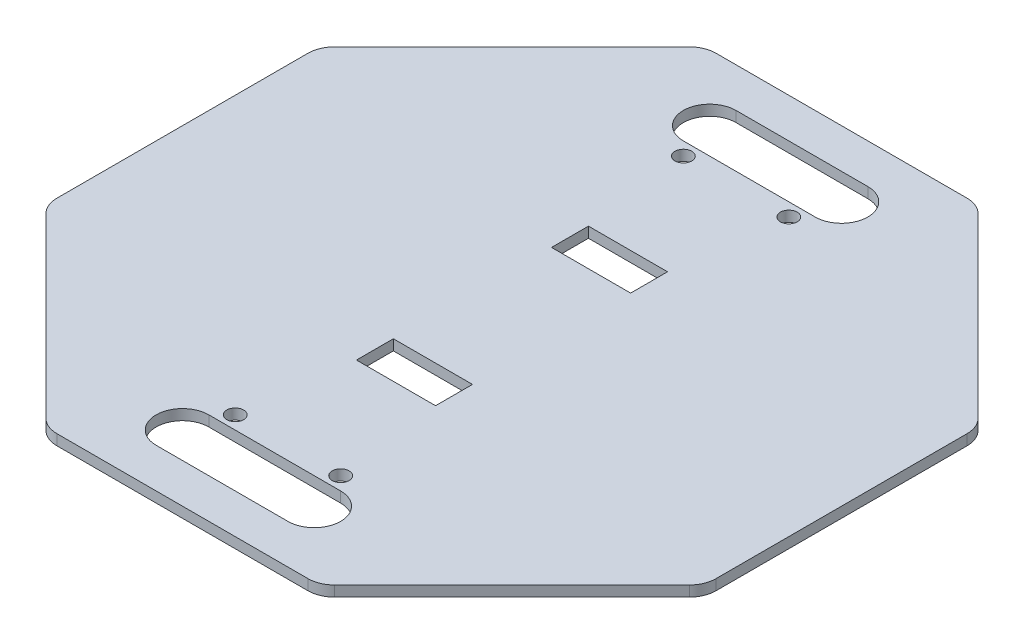
SolidWorks part; units mm, degrees
ref_plane "Front Plane" through (0, 0, 0) normal (0, 0, 1) x (1, 0, 0)
ref_plane "Top Plane" through (0, 0, 0) normal (0, 1, 0) x (1, 0, 0)
ref_plane "Right Plane" through (0, 0, 0) normal (1, 0, 0) x (0, 0, -1)
sketch "Sketch1" plane through (0, 0, 0) normal (0, 1, 0) x (1, 0, 0)
  line L0 (0, 67.6495) -> (0, -67.6495) construction
  line L1 (-67.6495, 0) -> (67.6495, 0) construction
  line L2 (62.5, 25.8883) -> (62.5, -25.8883)
  line L3 (-25.8883, 62.5) -> (25.8883, 62.5)
  line L4 (0, 0) -> (62.5, 25.8883) construction
  line L5 (-25.8883, 62.5) -> (0, 0) construction
  line L6 (-25.8883, -62.5) -> (25.8883, -62.5)
  line L7 (-62.5, 25.8883) -> (-62.5, -25.8883)
  line L8 (12.5, -50) -> (-12.5, -50) construction
  line L9 (12.5, -55) -> (-12.5, -55)
  line L10 (12.5, -45) -> (-12.5, -45)
  line L11 (12.5, 50) -> (-12.5, 50) construction
  line L12 (12.5, 55) -> (-12.5, 55)
  line L13 (12.5, 45) -> (-12.5, 45)
  line L14 (14.3249, -42.5) -> (-21.367, -42.5) construction
  line L15 (-7.5, -22) -> (7.5, -22)
  line L16 (-7.5, -22) -> (-7.5, -15)
  line L17 (-7.5, -15) -> (7.5, -15)
  line L18 (7.5, -22) -> (7.5, -15)
  line L19 (-7.5, -22) -> (7.5, -15) construction
  line L20 (-7.5, -15) -> (7.5, -22) construction
  line L21 (-7.5, 22) -> (-7.5, 15)
  line L22 (-7.5, 22) -> (7.5, 22)
  line L23 (7.5, 22) -> (7.5, 15)
  line L24 (-7.5, 15) -> (7.5, 15)
  line L25 (25.8883, -62.5) -> (62.5, -25.8883)
  line L26 (62.5, 25.8883) -> (25.8883, 62.5)
  line L27 (-25.8883, 62.5) -> (-62.5, 25.8883)
  line L28 (-62.5, -25.8883) -> (-25.8883, -62.5)
  circle A0 centre (0, 0) radius 67.6495
  arc A1 (12.5, -55) -> (12.5, -45) centre (12.5, -50) ccw
  arc A2 (-12.5, -45) -> (-12.5, -55) centre (-12.5, -50) ccw
  arc A3 (12.5, 55) -> (12.5, 45) centre (12.5, 50) cw
  arc A4 (-12.5, 45) -> (-12.5, 55) centre (-12.5, 50) cw
  circle A5 centre (10, -42.5) radius 1.6
  circle A6 centre (-10, -42.5) radius 1.6
  circle A7 centre (-10, 42.5) radius 1.6
  circle A8 centre (10, 42.5) radius 1.6
  point P17 (0, -50)
  point P24 (0, 50)
  point P29 (0, -18.5)
  dimension "D10" = 3.2
  dimension "D11" = 10
  dimension "D12" = 2.5
  dimension "D2" = 22.5
  dimension "D3" = 22.5
  dimension "D4" = 10
  dimension "D5" = 25
  dimension "D6" = 50
  dimension "D7" = 7
  dimension "D8" = 23
  dimension "D9" = 15
  dimension "D13" = 125
extrude "Boss-Extrude1" add sketch "Sketch1" along normal blind 2 contours L6 A0 L2 L3 L7 region at (0, 0, 0)
fillet "Fillet1" radius 5 8 edges at (-25.8883, 1, 62.5) (-62.5, 1, 25.8883) (-62.5, 1, -25.8883) (-25.8883, 1, -62.5) (25.8883, 1, -62.5) (62.5, 1, -25.8883) (62.5, 1, 25.8883) (25.8883, 1, 62.5)
